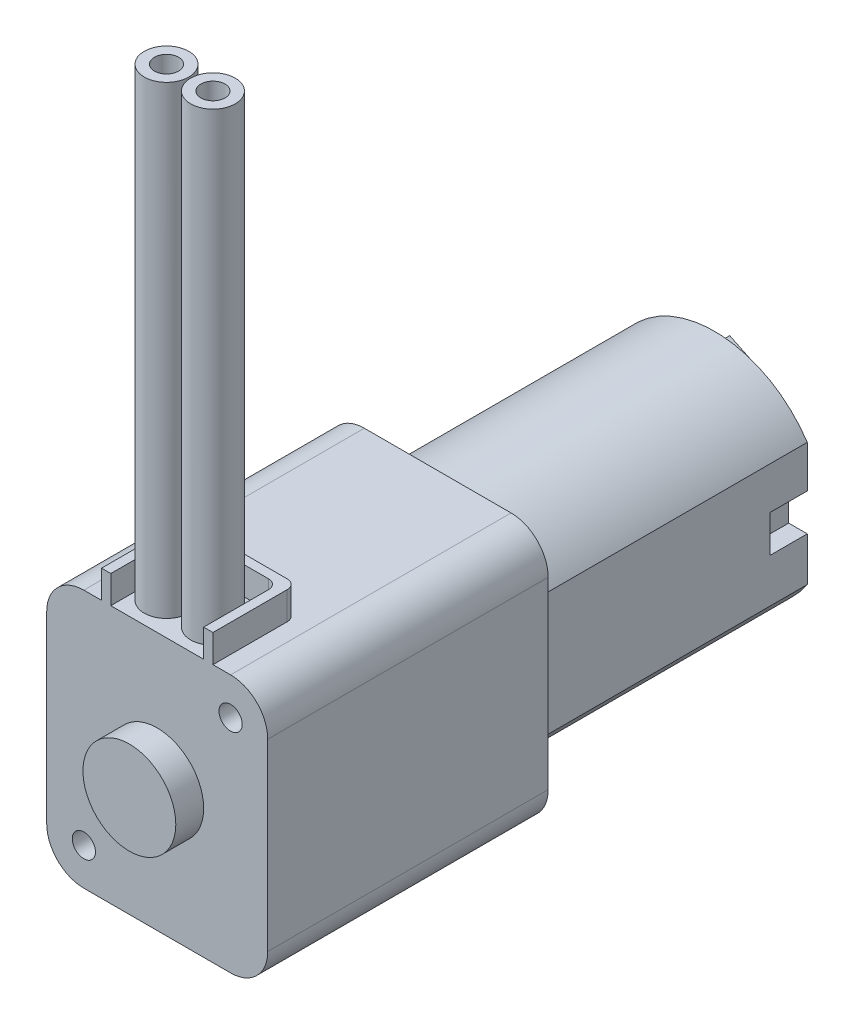
SolidWorks part; units mm, degrees
ref_plane "正面" through (0, 0, 0) normal (0, 0, 1) x (1, 0, 0)
ref_plane "平面" through (0, 0, 0) normal (0, 1, 0) x (1, 0, 0)
ref_plane "右側面" through (0, 0, 0) normal (1, 0, 0) x (0, 0, -1)
sketch "ｽｹｯﾁ1" plane through (0, 0, 0) normal (0, 0, 1) x (1, 0, 0)
  line L1 (-40.1948, 23.2736) -> (-32.2948, 23.2736)
  line L2 (-42.1948, 21.2736) -> (-42.1948, 11.3736)
  line L3 (-40.1948, 9.3736) -> (-32.2948, 9.3736)
  line L4 (-30.2948, 21.2736) -> (-30.2948, 11.3736)
  arc A0 (-30.2948, 21.2736) -> (-32.2948, 23.2736) centre (-32.2948, 21.2736) ccw
  arc A1 (-42.1948, 11.3736) -> (-40.1948, 9.3736) centre (-40.1948, 11.3736) ccw
  arc A2 (-32.2948, 9.3736) -> (-30.2948, 11.3736) centre (-32.2948, 11.3736) ccw
  arc A3 (-40.1948, 23.2736) -> (-42.1948, 21.2736) centre (-40.1948, 21.2736) ccw
  point P6 (-30.2948, 23.2736)
  point P11 (-30.2948, 9.3736)
  point P14 (-42.1948, 23.2736)
  dimension "D3" = 2
  dimension "D1" = 11.9
  dimension "D2" = 13.9
extrude "ﾎﾞｽ - 押し出し1" add sketch "ｽｹｯﾁ1" along normal blind 15.1
sketch "ｽｹｯﾁ2" plane through (0, 0, 15.1) normal (0, 0, 1) x (1, 0, 0)
  circle A0 centre (-36.2448, 16.3236) radius 2.5
  dimension "D1" = 5
extrude "ﾎﾞｽ - 押し出し2" add sketch "ｽｹｯﾁ2" along normal blind 1.5
sketch "ｽｹｯﾁ3" plane through (0, 23.2736, 0) normal (0, 1, 0) x (1, 0, 0)
  line L0 (-32.2948, -15.1) -> (-40.1948, -15.1) construction
  line L1 (-38.7448, -10.6) -> (-33.7448, -10.6)
  line L2 (-39.2448, -11.1) -> (-39.2448, -15.1)
  line L3 (-39.2448, -15.1) -> (-33.2448, -15.1)
  line L4 (-33.2448, -11.1) -> (-33.2448, -15.1)
  line L5 (-38.7448, -15.1) -> (-38.7448, -16.6) construction
  line L6 (-38.2448, -11.1) -> (-34.2448, -11.1)
  line L7 (-33.7448, -11.6) -> (-33.7448, -14.6)
  line L8 (-38.7448, -14.6) -> (-33.7448, -14.6)
  line L9 (-38.7448, -11.6) -> (-38.7448, -14.6)
  line L10 (-33.7448, -11.1) -> (-33.7448, -14.6) construction
  line L11 (-38.7448, -11.1) -> (-33.7448, -11.1) construction
  line L12 (-38.7448, -11.1) -> (-38.7448, -14.6) construction
  line L13 (-38.7448, -14.6) -> (-38.7448, -15.1)
  line L14 (-33.7448, -14.6) -> (-33.7448, -15.1)
  arc A0 (-33.2448, -11.1) -> (-33.7448, -10.6) centre (-33.7448, -11.1) ccw
  arc A1 (-39.2448, -11.1) -> (-38.7448, -10.6) centre (-38.7448, -11.1) cw
  arc A2 (-38.2448, -11.1) -> (-38.7448, -11.6) centre (-38.2448, -11.6) ccw
  arc A4 (-33.7448, -11.6) -> (-34.2448, -11.1) centre (-34.2448, -11.6) ccw
  arc A5 (-33.7448, -11.1) -> (-33.7448, -11.1) centre (-33.7448, -11.1) ccw construction
  arc A6 (-38.7448, -11.1) -> (-38.7448, -11.1) centre (-38.7448, -11.1) cw construction
  point P10 (-33.2448, -10.6)
  line M3 (-40.1948, -15.1) -> (-32.2948, -15.1)
  dimension "D4" = 0.5
  dimension "D6" = 0.5
  dimension "D1" = 6
  dimension "D2" = 4.5
  dimension "D3" = 0.5
  dimension "D5" = 0.5
extrude "ﾎﾞｽ - 押し出し3" add sketch "ｽｹｯﾁ3" along normal blind 1.5 contours A4 L7 L14 L4 A0 L1 A1 L2 L13 L9 A2 L6 M3 region at (-36.2448, 23.2736, 10.675)
sketch "ｽｹｯﾁ4" plane through (0, 0, 15.1) normal (0, 0, 1) x (1, 0, 0)
  point P0 (-40.1948, 21.2736)
  point P1 (-32.2948, 21.2736)
  point P3 (-32.2948, 11.3736)
  point P5 (-40.1948, 11.3736)
hole_wizard "M1.6x0.35 ねじ穴1" positions "3Dｽｹｯﾁ1" profile "ｽｹｯﾁ5" tap size "M1.6x0.35" standard "JIS"
sketch3d "3Dｽｹｯﾁ1"
  point P0 (-32.2948, 21.2736, 15.1)
  point P3 (-40.1948, 11.3736, 15.1)
sketch "ｽｹｯﾁ5" plane through (-32.2948, 21.2736, 15.1) normal (1, 0, 0) x (0, -1, 0)
  line L0 (0, 0) -> (0, 5.3255)
  line L1 (0, 5.3255) -> (0.625, 4.95)
  line L2 (0.625, 4.95) -> (0.625, 0)
  line L5 (0.625, 0) -> (0, 0)
  line L10 (0, 5.3255) -> (-0.625, 4.95) construction
  line L11 (0, -6.35) -> (0, 107.95) construction
  dimension "ねじ下穴ﾄﾞﾘﾙ直径" = 1.25
  dimension "ねじ下穴ﾄﾞﾘﾙの深さ" = 4.95
  dimension "ﾄﾞﾘﾙ角度" = 118
cosmetic thread "穴のねじ山1" parameters "D1"=3.2, "D2"=1.6
cosmetic thread "穴のねじ山2" parameters "D1"=3.2, "D2"=1.6
sketch "ｽｹｯﾁ7" plane through (0, 0, 0) normal (0, 0, -1) x (-1, 0, 0)
  line L0 (30.2948, 11.3736) -> (30.2948, 21.2736) construction
  line L1 (32.2448, 22.3736) -> (40.2448, 22.3736)
  line L2 (31.2448, 21.3736) -> (31.2448, 11.3736)
  line L3 (32.2448, 10.3736) -> (40.2448, 10.3736)
  line L4 (41.2448, 21.3736) -> (41.2448, 11.3736)
  line L5 (40.1948, 9.3736) -> (32.2948, 9.3736) construction
  line L6 (36.2448, 25.738) -> (36.2448, 6.413) construction
  line L7 (31.2448, 16.3736) -> (31.2448, 17.3736)
  line L8 (31.2448, 17.3736) -> (32.2448, 17.3736)
  line L9 (32.2448, 17.3736) -> (32.2448, 15.3736)
  line L10 (32.2448, 15.3736) -> (31.2448, 15.3736)
  line L11 (40.2448, 15.3736) -> (41.2448, 15.3736)
  line L12 (40.2448, 17.3736) -> (40.2448, 15.3736)
  line L13 (41.2448, 17.3736) -> (40.2448, 17.3736)
  arc A0 (31.2448, 13.007) -> (41.2448, 13.007) centre (36.2448, 16.3236) ccw
  arc A1 (41.2448, 19.6402) -> (31.2448, 19.6402) centre (36.2448, 16.3236) ccw
  arc A4 (40.2448, 10.3736) -> (41.2448, 11.3736) centre (40.2448, 11.3736) ccw
  arc A5 (32.2448, 10.3736) -> (31.2448, 11.3736) centre (32.2448, 11.3736) cw
  arc A6 (41.2448, 21.3736) -> (40.2448, 22.3736) centre (40.2448, 21.3736) ccw
  arc A7 (31.2448, 21.3736) -> (32.2448, 22.3736) centre (32.2448, 21.3736) cw
  point P10 (41.2448, 10.3736)
  point P13 (41.2448, 22.3736)
  point P16 (31.2448, 10.3736)
  dimension "D5" = 2
  dimension "D6" = 1
  dimension "D1" = 10
  dimension "D2" = 12
  dimension "D3" = 0.95
  dimension "D4" = 1
  dimension "D7" = 1
  dimension "D8" = 1
extrude "ﾎﾞｽ - 押し出し4" add sketch "ｽｹｯﾁ7" along normal blind 14.9 contours L6 A1 L2 L8 L9 L10 A0 L3 | A1 L6 L3 A0 L4 L11 L12 L13 region at (-38.4573, 16.3247, 0) region at (-34.0324, 16.3247, 0)
extrude "ﾎﾞｽ - 押し出し5" add sketch "ｽｹｯﾁ7<3>" along normal blind 12.9 contours L10 L9 L8 L2 | L4 L13 L12 L11 region at (-31.7448, 16.3736, 0) region at (-40.7448, 16.3736, 0)
sketch "ｽｹｯﾁ7<3>" plane through (0, 0, 0) normal (0, 0, -1) x (-1, 0, 0) same geometry as "ｽｹｯﾁ7"
sketch "ｽｹｯﾁ8" plane through (0, 0, -14.9) normal (0, 0, -1) x (-1, 0, 0)
  line L0 (36.2448, 12.8831) -> (36.2448, 22.6099) construction
  line L1 (36.2448, 22.6099) -> (36.2448, 8.926) construction
  line L2 (35.5693, 20.3766) -> (36.9204, 21.028) construction
  line L3 (36.9204, 21.028) -> (37.0055, 20.8516) construction
  line L4 (37.0055, 20.8516) -> (35.6543, 20.2002) construction
  line L5 (35.6543, 20.2002) -> (35.5693, 20.3766) construction
  line L6 (35.5693, 20.3766) -> (36.9204, 21.028)
  line L7 (36.9204, 21.028) -> (37.0055, 20.8516)
  line L8 (37.0055, 20.8516) -> (35.6543, 20.2002)
  line L9 (35.6543, 20.2002) -> (35.5693, 20.3766)
  line L10 (36.2448, 20.7023) -> (36.3299, 20.5259) construction
  line L11 (29.8543, 16.3236) -> (43.7997, 16.3236) construction
  line L21 (36.9204, 12.2707) -> (35.5693, 11.6192) construction
  line L22 (35.5693, 11.6192) -> (35.4842, 11.7956) construction
  line L23 (35.4842, 11.7956) -> (36.8354, 12.447) construction
  line L24 (36.8354, 12.447) -> (36.9204, 12.2707) construction
  line L25 (36.2448, 11.945) -> (36.1598, 12.1213) construction
  line L26 (36.9204, 12.2707) -> (35.5693, 11.6192)
  line L27 (35.5693, 11.6192) -> (35.4842, 11.7956)
  line L28 (35.4842, 11.7956) -> (36.8354, 12.447)
  line L29 (36.8354, 12.447) -> (36.9204, 12.2707)
  circle A0 centre (36.2448, 16.3236) radius 2
  dimension "D1" = 0.75
  dimension "D2" = 0.75
  dimension "D3" = 0.1764
extrude "ﾎﾞｽ - 押し出し6" add sketch "ｽｹｯﾁ8" along normal blind 1.1 contours A0 region at (-36.2448, 16.3236, -14.9)
extrude "ﾎﾞｽ - 押し出し7" add sketch "ｽｹｯﾁ8<3>" along normal blind 1.5 contours L9 L8 L7 L6 | L29 L28 L27 L26 region at (-36.2874, 20.6141, -14.9) region at (-36.2023, 12.0331, -14.9)
sketch "ｽｹｯﾁ8<3>" plane through (0, 0, -14.9) normal (0, 0, -1) x (-1, 0, 0) same geometry as "ｽｹｯﾁ8"
sketch "ｽｹｯﾁ10" plane through (0, 23.2736, 0) normal (0, 1, 0) x (1, 0, 0)
  line L0 (-38.7448, -11.6) -> (-38.7448, -15.1) construction
  line L1 (-33.7448, -11.6) -> (-33.7448, -15.1) construction
  circle A0 centre (-37.4948, -13.35) radius 1.2
  circle A1 centre (-34.9948, -13.35) radius 1.2
  circle A2 centre (-37.4948, -13.35) radius 0.65
  circle A3 centre (-34.9948, -13.35) radius 0.65
  dimension "D1" = 2.4
  dimension "D2" = 2.4
  dimension "D3" = 1.25
  dimension "D4" = 1.25
  dimension "D5" = 0.55
extrude "ﾎﾞｽ - 押し出し13" add sketch "ｽｹｯﾁ10" along normal blind 25 contours A0 A2 | A1 A3 region at (-38.6609, 23.2736, 13.35) region at (-36.1609, 23.2736, 13.35)
